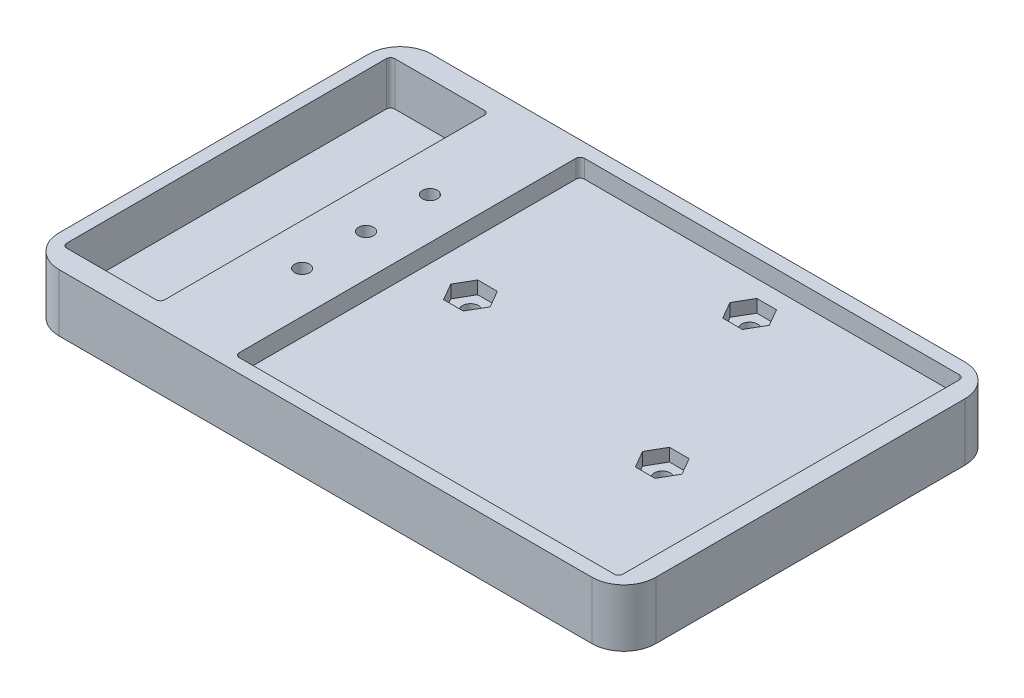
SolidWorks part; units mm, degrees
ref_plane "Front Plane" through (0, 0, 0) normal (0, 0, 1) x (1, 0, 0)
ref_plane "Top Plane" through (0, 0, 0) normal (0, 1, 0) x (1, 0, 0)
ref_plane "Right Plane" through (0, 0, 0) normal (1, 0, 0) x (0, 0, -1)
sketch "Sketch1" plane through (0, 0, 0) normal (0, 1, 0) x (1, 0, 0)
  line L1 (0, 0) -> (140, 0)
  line L2 (0, 0) -> (0, 87.5)
  line L3 (0, 87.5) -> (140, 87.5)
  line L4 (140, 0) -> (140, 87.5)
  dimension "D1" = 87.5
  dimension "D2" = 140
extrude "Boss-Extrude1" add sketch "Sketch1" along normal blind 13.5
sketch "Sketch2" plane through (0, 13.5, 0) normal (0, 1, 0) x (1, 0, 0)
  line L5 (140, 43.75) -> (135.5, 43.75) construction
  line L7 (45.5, 84.25) -> (135.5, 84.25)
  line L9 (45.5, 84.25) -> (45.5, 3.25)
  line L10 (45.5, 3.25) -> (135.5, 3.25)
  line L11 (135.5, 84.25) -> (135.5, 3.25)
  line L12 (140, 0) -> (140, 87.5) construction
  line L13 (90.5, 84.25) -> (90.5, 87.5) construction
  line L14 (140, 87.5) -> (0, 87.5) construction
  line L15 (90.5, 3.25) -> (90.5, 0) construction
  line L16 (0, 0) -> (140, 0) construction
  dimension "D3" = 81
  dimension "D1" = 4.5
  dimension "D2" = 90
extrude "Cut-Extrude1" cut sketch "Sketch2" against normal blind 4.25
sketch "Sketch5" plane through (0, 13.5, 0) normal (0, 1, 0) x (1, 0, 0)
  line L0 (0, 87.5) -> (0, 0) construction
  line L1 (3, 5.25) -> (26, 5.25)
  line L2 (3, 5.25) -> (3, 82.25)
  line L3 (3, 82.25) -> (26, 82.25)
  line L4 (26, 5.25) -> (26, 82.25)
  line L5 (14.5, 82.25) -> (14.5, 87.5) construction
  line L6 (140, 87.5) -> (0, 87.5) construction
  line L7 (14.5, 5.25) -> (14.5, 0) construction
  line L8 (0, 0) -> (140, 0) construction
  dimension "D1" = 23
  dimension "D2" = 77
  dimension "D3" = 3
extrude "Cut-Extrude2" cut sketch "Sketch5" against normal blind 10.25
sketch "Sketch11" plane through (0, 9.25, 0) normal (0, 1, 0) x (1, 0, 0)
  line L0 (90.5, 84.25) -> (90.5, 3.25) construction
  line L1 (135.5, 84.25) -> (45.5, 84.25) construction
  line L2 (45.5, 3.25) -> (135.5, 3.25) construction
  line L3 (45.5, 43.75) -> (135.5, 43.75) construction
  line L4 (45.5, 84.25) -> (45.5, 3.25) construction
  line L5 (135.5, 3.25) -> (135.5, 84.25) construction
  line L7 (90.5, 43.75) -> (56.75, 43.75) construction
  line L8 (90.5, 43.75) -> (90.5, 47.25) construction
  line L9 (90.5, 47.25) -> (56.75, 47.25) construction
  line L10 (56.75, 43.75) -> (56.75, 47.25) construction
  line L15 (90.5, 43.75) -> (113.25, 43.75) construction
  line L16 (90.5, 43.75) -> (90.5, 35.75) construction
  line L17 (90.5, 35.75) -> (113.25, 35.75) construction
  line L18 (113.25, 43.75) -> (113.25, 35.75) construction
  line L19 (90.5, 43.75) -> (93.25, 43.75) construction
  line L20 (90.5, 43.75) -> (90.5, 76.25) construction
  line L21 (90.5, 76.25) -> (93.25, 76.25) construction
  line L22 (93.25, 43.75) -> (93.25, 76.25) construction
  dimension "D1" = 3.5
  dimension "D2" = 33.75
  dimension "D3" = 32.5
  dimension "D4" = 2.75
  dimension "D5" = 8
  dimension "D6" = 22.75
hole_wizard "#6 Clearance Hole1" positions "Sketch17" profile "Sketch18" hole size "#6" standard "ANSI Inch" end condition through all
sketch "Sketch17" plane through (0, 9.25, 0) normal (0, 1, 0) x (1, 0, 0)
  point P0 (56.75, 47.25)
  point P3 (93.25, 76.25)
  point P6 (113.25, 35.75)
sketch "Sketch18" plane through (56.75, 9.25, -47.25) normal (1, 0, 0) x (0, 0, 1)
  line L0 (0, 0) -> (0, 9.25)
  line L1 (0, 9.25) -> (1.8986, 9.25)
  line L2 (1.8986, 9.25) -> (1.8986, 0)
  line L5 (1.8986, 0) -> (0, 0)
  line L11 (0, -6.35) -> (0, 107.95) construction
  dimension "Thru Hole Dia." = 3.7973
  dimension "Thru Hole Depth" = 9.25
sketch "Sketch19" plane through (0, 9.25, 0) normal (0, 1, 0) x (1, 0, 0)
  line L0 (135.5, 84.25) -> (45.5, 84.25) construction
  line L1 (59.0594, 51.25) -> (54.4406, 51.25)
  line L2 (54.4406, 51.25) -> (52.1312, 47.25)
  line L3 (52.1312, 47.25) -> (54.4406, 43.25)
  line L4 (54.4406, 43.25) -> (59.0594, 43.25)
  line L5 (59.0594, 43.25) -> (61.3688, 47.25)
  line L6 (61.3688, 47.25) -> (59.0594, 51.25)
  line L7 (97.8688, 76.25) -> (95.5594, 80.25)
  line L8 (95.5594, 80.25) -> (90.9406, 80.25)
  line L9 (90.9406, 80.25) -> (88.6312, 76.25)
  line L10 (88.6312, 76.25) -> (90.9406, 72.25)
  line L11 (90.9406, 72.25) -> (95.5594, 72.25)
  line L12 (95.5594, 72.25) -> (97.8688, 76.25)
  line L13 (117.8688, 35.75) -> (115.5594, 39.75)
  line L14 (115.5594, 39.75) -> (110.9406, 39.75)
  line L15 (110.9406, 39.75) -> (108.6312, 35.75)
  line L16 (108.6312, 35.75) -> (110.9406, 31.75)
  line L17 (110.9406, 31.75) -> (115.5594, 31.75)
  line L18 (115.5594, 31.75) -> (117.8688, 35.75)
  line L19 (135.5, 84.25) -> (45.5, 84.25) construction
  circle A0 centre (56.75, 47.25) radius 4 construction
  circle A1 centre (93.25, 76.25) radius 4 construction
  circle A2 centre (113.25, 35.75) radius 4 construction
  dimension "D1" = 8
extrude "Cut-Extrude4" cut sketch "Sketch19" against normal blind 3
fillet "Fillet1" radius 7.5 4 edges at (0, 6.75, 0) (0, 6.75, -87.5) (140, 6.75, -87.5) (140, 6.75, 0)
sketch "Sketch15" plane through (0, 13.5, 0) normal (0, 1, 0) x (1, 0, 0)
  line L0 (26, 43.75) -> (45.5, 43.75) construction
  line L9 (26, 5.25) -> (26, 82.25) construction
  line L10 (45.5, 3.25) -> (45.5, 84.25) construction
  line L12 (35.75, 43.75) -> (35.75, 58.75) construction
  line L14 (35.75, 43.75) -> (35.75, 28.75) construction
  line L15 (132.5, 87.5) -> (7.5, 87.5) construction
  line L17 (7.5, 0) -> (132.5, 0) construction
  line L26 (70, 87.5) -> (70, 0) construction
  circle A4 centre (35.75, 43.75) radius 1.75
  circle A5 centre (35.75, 58.75) radius 1.75
  circle A6 centre (35.75, 28.75) radius 1.75
  dimension "D2" = 3.5
  dimension "D1" = 15
extrude "Cut-Extrude3" cut sketch "Sketch15" against normal blind 7.5
fillet "Fillet2" radius 1 8 edges at (3, 8.375, -5.25) (26, 8.375, -5.25) (26, 8.375, -82.25) (3, 8.375, -82.25) (135.5, 11.375, -3.25) (45.5, 11.375, -3.25) (135.5, 11.375, -84.25) (45.5, 11.375, -84.25)
